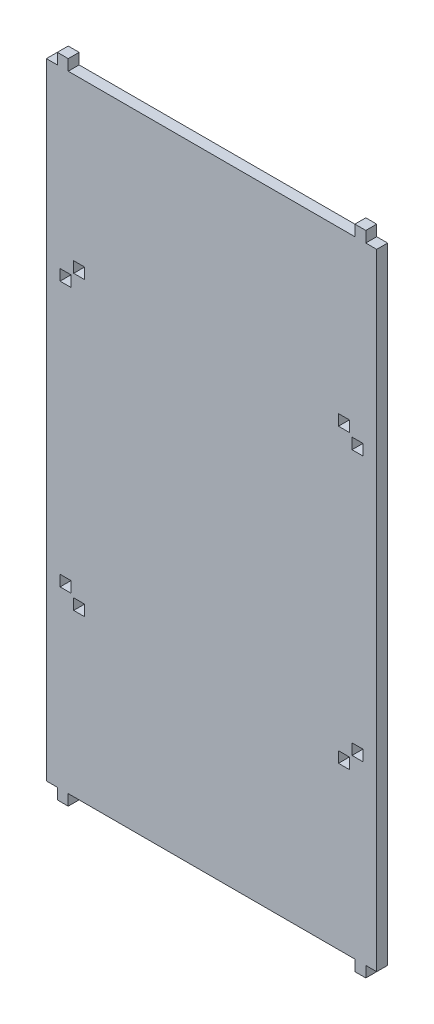
SolidWorks part; units mm, degrees
ref_plane "Front Plane" through (0, 0, 0) normal (0, 0, 1) x (1, 0, 0)
ref_plane "Top Plane" through (0, 0, 0) normal (0, 1, 0) x (1, 0, 0)
ref_plane "Right Plane" through (0, 0, 0) normal (1, 0, 0) x (0, 0, -1)
sketch "Sketch1" plane through (0, 0, 0) normal (0, 0, 1) x (1, 0, 0)
  line L0 (0, -0.9075) -> (0, 0.9075) construction
  line L1 (-23.3, 48.9) -> (23.3, 48.9)
  line L2 (-23.3, 48.9) -> (-23.3, -48.9)
  line L3 (-23.3, -48.9) -> (23.3, -48.9)
  line L4 (23.3, 48.9) -> (23.3, -48.9)
  line L5 (0.9075, 0) -> (-0.9075, 0) construction
  point P5 (0, 48.9)
  point P8 (23.3, 0)
  dimension "D1" = 97.8
  dimension "D2" = 46.6
extrude "Boss-Extrude1" add sketch "Sketch1" along normal blind 1.65
sketch "Sketch3" plane through (-23.3, 0, 0) normal (-1, 0, 0) x (0, 0, 1)
  line L0 (1.65, 48.9) -> (1.65, -48.9) construction
  line L1 (1.65, 47.25) -> (0, 47.25)
  line L2 (1.65, 47.25) -> (1.65, -47.25)
  line L3 (1.65, -47.25) -> (0, -47.25)
  line L4 (0, 47.25) -> (0, -47.25)
  line L5 (0, 48.9) -> (0, -48.9) construction
  line L6 (1.65, -48.9) -> (0, -48.9) construction
  line L7 (1.65, 48.9) -> (0, 48.9) construction
  dimension "D1" = 1.65
  dimension "D2" = 1.65
extrude "Boss-Extrude2" add sketch "Sketch3" along normal blind 1.65
mirror "Mirror1" about plane through (0, 0, 0) normal (1, 0, 0) of "Boss-Extrude2"
sketch "Sketch2" plane through (0, 0, 1.65) normal (0, 0, 1) x (1, 0, 0)
  line L0 (0.9075, 0) -> (-0.9075, 0) construction
  line L1 (21.225, 20.825) -> (22.875, 20.825)
  line L2 (21.225, 20.825) -> (21.225, -20.825)
  line L3 (21.225, -20.825) -> (22.875, -20.825)
  line L4 (22.875, 20.825) -> (22.875, -20.825)
  line L5 (22.875, -20.825) -> (21.225, -19.175) construction
  line L7 (20.825, -21.225) -> (20.825, -22.875)
  line L8 (20.825, -21.225) -> (-20.825, -21.225)
  line L9 (-20.825, -21.225) -> (-20.825, -22.875)
  line L10 (20.825, -22.875) -> (-20.825, -22.875)
  line L11 (-21.225, -20.825) -> (-22.875, -20.825)
  line L12 (-21.225, -20.825) -> (-21.225, 20.825)
  line L13 (-21.225, 20.825) -> (-22.875, 20.825)
  line L14 (-22.875, -20.825) -> (-22.875, 20.825)
  line L15 (-20.825, 21.225) -> (-20.825, 22.875)
  line L16 (-20.825, 21.225) -> (20.825, 21.225)
  line L17 (20.825, 21.225) -> (20.825, 22.875)
  line L18 (-20.825, 22.875) -> (20.825, 22.875)
  line L19 (21.225, 19.175) -> (22.875, 19.175)
  line L20 (21.225, -19.175) -> (22.875, -19.175)
  line L21 (-19.175, -21.225) -> (-19.175, -22.875)
  line L22 (19.175, -21.225) -> (19.175, -22.875)
  line L23 (-21.225, 19.175) -> (-22.875, 19.175)
  line L24 (-21.225, -19.175) -> (-22.875, -19.175)
  line L25 (19.175, 21.225) -> (19.175, 22.875)
  line L26 (-19.175, 21.225) -> (-19.175, 22.875)
  line L27 (22.875, 20.825) -> (21.225, 19.175) construction
  line L28 (22.875, 19.175) -> (21.225, 20.825) construction
  line L29 (22.875, -19.175) -> (21.225, -20.825) construction
  line L30 (0, -0.9075) -> (0, 0.9075) construction
  point P4 (22.875, 0)
  point P10 (22.05, -20)
  point P26 (22.05, 20)
  dimension "D1" = 1.65
  dimension "D5" = 1.65
  dimension "D6" = 1.65
  dimension "D3" = 22.05
  dimension "D2" = 40
  dimension "D4" = 4
  dimension "D7" = 4
extrude "Cut-Extrude1" cut sketch "Sketch2" against normal blind 1.65 contours L8 L22 L10 L7 | L21 L8 L9 L10 | L12 L24 L14 L11 | L23 L12 L13 L14 | L16 L26 L18 L15 | L25 L16 L17 L18 | L2 L19 L4 L1 | L20 L2 L3 L4 region at (22.05, 20, 1.65) region at (22.05, -20, 1.65) region at (20, -22.05, 1.65) region at (-20, -22.05, 1.65) region at (-22.05, -20, 1.65) region at (-22.05, 20, 1.65) region at (-20, 22.05, 1.65) region at (20, 22.05, 1.65)
sketch "Sketch4" plane through (0, -48.9, 0) normal (0, -1, 0) x (1, 0, 0)
  line L0 (-23.3, 1.65) -> (23.3, 1.65) construction
  line L1 (-21.65, 1.65) -> (21.65, 1.65)
  line L2 (-21.65, 1.65) -> (-21.65, 0)
  line L3 (-21.65, 0) -> (21.65, 0)
  line L4 (21.65, 1.65) -> (21.65, 0)
  line L5 (-23.3, 0) -> (23.3, 0) construction
  line L6 (23.3, 0) -> (23.3, 1.65) construction
  line L7 (-23.3, 1.65) -> (-23.3, 0) construction
  dimension "D1" = 1.65
  dimension "D2" = 1.65
extrude "Cut-Extrude2" cut sketch "Sketch4" against normal blind 1.65
mirror "Mirror2" about plane through (0, 0, 0) normal (0, 1, 0) of "Cut-Extrude2"
equation "\"D1@Sketch1\"=3/8 * \"lenght\" + \"PCB Thickness\" * 2"
equation "\"Dinoskin scale\"= 2.2"
equation "\"pattern X\"= 3"
equation "\"Pattern Y\"= 9"
equation "\"Base Innerline\"= 0.34"
equation "\"lenght\"= 252"
equation "\"PCB Thickness\"= 1.65"
equation "\"Base Width\"= 4.5"
equation "\"Base Outerline\"= 1"
equation "\"Base Inner to Outer\"= 1"
equation "\"Dinoskin Outerline\"= \"Base Outerline\" * \"Dinoskin scale\""
equation "\"Dinoskin Innerline\"= \"Base Innerline\" * \"Dinoskin scale\""
equation "\"Dinoskin Width\"= \"Base Width\" * \"Dinoskin scale\""
equation "\"Dinoskin Inner to Outer\"= \"Base Inner to Outer\" * \"Dinoskin scale\""
equation "\"Diagonal dist\"= \"Dinoskin Width\" + ( ( \"Dinoskin Innerline\" + \"Dinoskin Outerline\" ) / 2 + \"Dinoskin Inner to Outer\" ) / cos ( 30 )"
equation "\"Dinoskin pattern Y\"= \"Diagonal dist\" * sin ( 30 )"
equation "\"Offset Y\"= 2 * \"Dinoskin pattern Y\""
equation "\"Diagonal dist 2\"= \"Dinoskin Width\" + ( ( \"Dinoskin Innerline\" + \"Dinoskin Outerline\" ) / 2 + 1 ) / cos ( 30 )"
equation "\"Dinoskin pattern X\"= \"Diagonal dist\" * cos ( 30 )"
equation "\"offset x\"= \"Dinoskin pattern X\" * 2"
equation "\"Pattern spacing X\"= \"offset x\" * ( \"pattern X\" - 0.5 ) / 2"
equation "\"Pattern spacing Y\"= \"Offset Y\" *  ( \"Pattern Y\" - 0.5 )  / 2 + 13"
equation "\"offset corner beams\" = 1"
equation "\"D2@Sketch1\"=40+  \"PCB Thickness\" * 4"
equation "\"D1@Boss-Extrude1\"= \"PCB Thickness\""
equation "\"D1@Sketch2\"= \"PCB Thickness\""
equation "\"D1@Sketch3\"= \"PCB Thickness\""
equation "\"D2@Sketch3\"=\"PCB Thickness\""
equation "\"D1@Boss-Extrude2\"=\"PCB Thickness\""
equation "\"D5@Sketch2\"= \"PCB Thickness\""
equation "\"D6@Sketch2\"=\"PCB Thickness\""
equation "\"D1@Sketch4\"= \"PCB Thickness\""
equation "\"D2@Sketch4\"= \"PCB Thickness\""
equation "\"D1@Cut-Extrude2\"= \"PCB Thickness\""
equation "\"D3@Sketch2\"=20 + 0.4 +\"PCB Thickness\""
